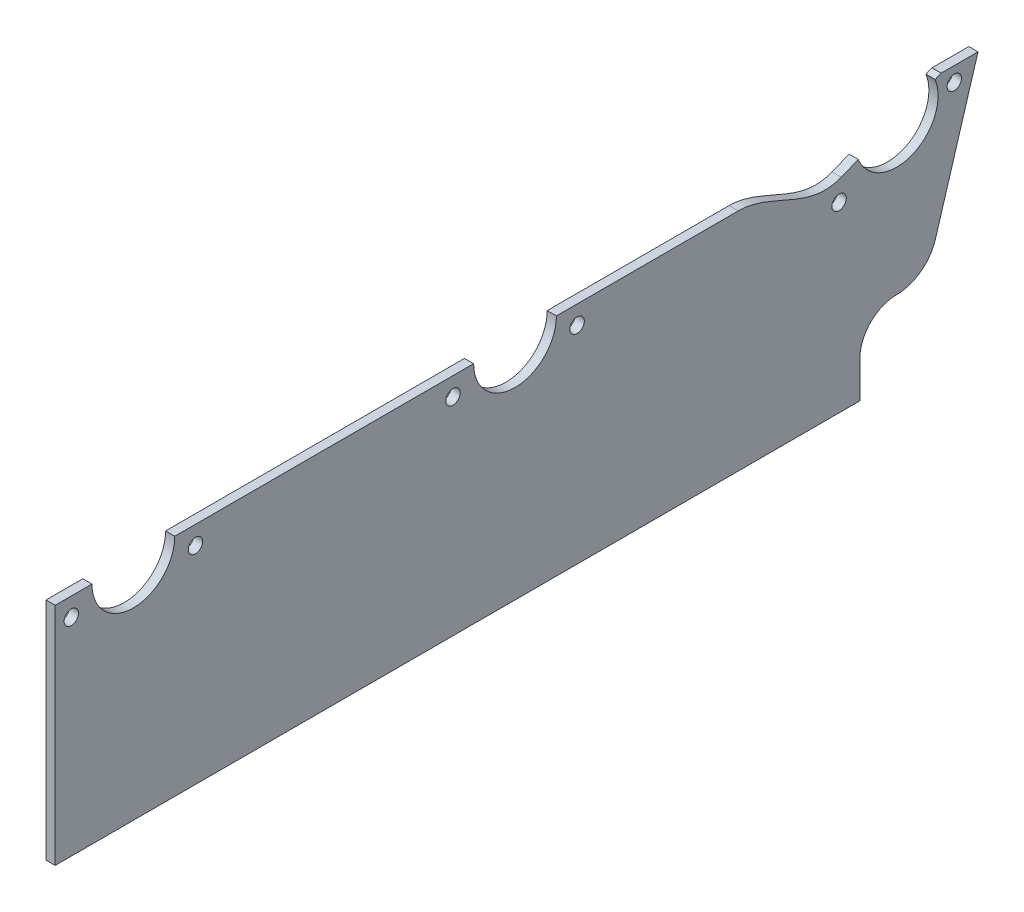
SolidWorks part; units mm, degrees
material "6061 Alloy"
ref_plane "Front Plane" through (0, 0, 0) normal (0, 0, 1) x (1, 0, 0)
ref_plane "Top Plane" through (0, 0, 0) normal (0, 1, 0) x (1, 0, 0)
ref_plane "Right Plane" through (0, 0, 0) normal (1, 0, 0) x (0, 0, -1)
sketch "Sketch1" plane through (0, 0, 0) normal (1, 0, 0) x (0, 0, -1)
  line L0 (-12.7, -12.7) -> (-290.5125, -12.7)
  line L1 (-290.5125, -12.7) -> (-290.5125, 65.0875)
  line L2 (-290.5125, 65.0875) -> (-277.8125, 65.0875)
  line L3 (-249.2375, 65.0875) -> (-146.05, 65.0875)
  line L5 (13.2588, 70.4107) -> (15.3674, 71.2572)
  line L7 (-290.5125, 12.7) -> (13.3728, 12.7) construction
  line L8 (-12.7, -12.7) -> (-12.7, 0)
  line L9 (0, 12.4079) -> (0, 12.7) construction
  line L10 (13.3728, 22.629) -> (28.0674, 71.2572)
  line L12 (-13.2588, 59.7643) -> (13.2588, 70.4107) construction
  line L13 (15.3674, 71.2572) -> (28.0674, 71.2572)
  line L14 (-117.475, 65.0875) -> (-54.7025, 65.0875)
  line L15 (-13.2588, 59.7643) -> (-19.1516, 57.3984)
  arc A3 (0, 12.7) -> (13.3728, 22.629) centre (0, 26.67) ccw
  arc A4 (0, 12.7) -> (-12.7, 0) centre (0, 0) ccw
  circle A5 centre (0, 0) radius 12.4079 construction
  arc A6 (-277.8125, 65.0875) -> (-249.2375, 65.0875) centre (-263.525, 65.0875) ccw
  arc A7 (-146.05, 65.0875) -> (-117.475, 65.0875) centre (-131.7625, 65.0875) ccw
  arc A8 (-13.2588, 59.7643) -> (13.2588, 70.4107) centre (0, 65.0875) ccw
  spline S0 degree 3 poles (-19.1516, 57.3984) (-30.9005, 52.6815) (-42.5782, 65.0875) (-54.7025, 65.0875) knots 0 0 0 0 1 1 1 1
  point P4 (-151.6062, -12.7)
  dimension "D1" = 25.4
  dimension "D3" = 12.7
  dimension "D5" = 28.575
  dimension "D6" = 38.1
  dimension "D7" = 13.97
  dimension "D8" = 12.7
  dimension "D10" = 24.8158
  dimension "D13" = 6.35
  dimension "D2" = 0
  dimension "D4" = 12.7
  dimension "D9" = 12.7
  dimension "D11" = 263.525
  dimension "D12" = 263.525
  dimension "D14" = 50.8
extrude "Boss-Extrude1" add sketch "Sketch1" along normal blind 3.175
hole_wizard "#10 Clearance Hole1" positions "Sketch2" profile "Sketch3" hole size "#10" standard "ANSI Inch" end condition through all
sketch "Sketch2" plane through (3.175, 0, 0) normal (1, 0, 0) x (0, 0, -1)
  line L0 (-284.9563, 58.7375) -> (-242.0938, 58.7375) construction
  line L2 (-153.1937, 58.7375) -> (-110.3312, 58.7375) construction
  line L4 (-19.8882, 50.26) -> (19.8882, 66.2296) construction
  line L6 (-277.8125, 65.0875) -> (-290.5125, 65.0875) construction
  line L7 (-263.525, 58.7375) -> (-263.525, 65.0875) construction
  line L9 (-131.7625, 65.0875) -> (-131.7625, 58.7375) construction
  line L11 (0, 65.0875) -> (0, 58.2448) construction
  line L14 (15.3674, 71.2572) -> (13.2588, 70.4107) construction
  line L15 (15.3674, 71.2572) -> (13.2588, 70.4107) construction
  point P0 (-284.9563, 58.7375)
  point P2 (-242.0938, 58.7375)
  point P4 (-153.1937, 58.7375)
  point P6 (-110.3312, 58.7375)
  point P8 (-19.8882, 50.26)
  point P10 (19.8882, 66.2296)
  point P45 (0, 0)
  point P46 (0, 0)
  point P47 (0, 61.025)
  point P48 (0, 0)
  dimension "D1" = 42.8625
  dimension "D2" = 6.35
  dimension "D3" = 6.35
sketch "Sketch3" plane through (3.175, 58.7375, 284.9563) normal (0, 1, 0) x (0, 0, -1)
  line L0 (0, 0) -> (0, 3.175)
  line L1 (0, 3.175) -> (2.4892, 3.175)
  line L2 (2.4892, 3.175) -> (2.4892, 0)
  line L5 (2.4892, 0) -> (0, 0)
  line L11 (0, -6.35) -> (0, 107.95) construction
  dimension "Thru Hole Dia." = 4.9784
  dimension "Thru Hole Depth" = 3.175
